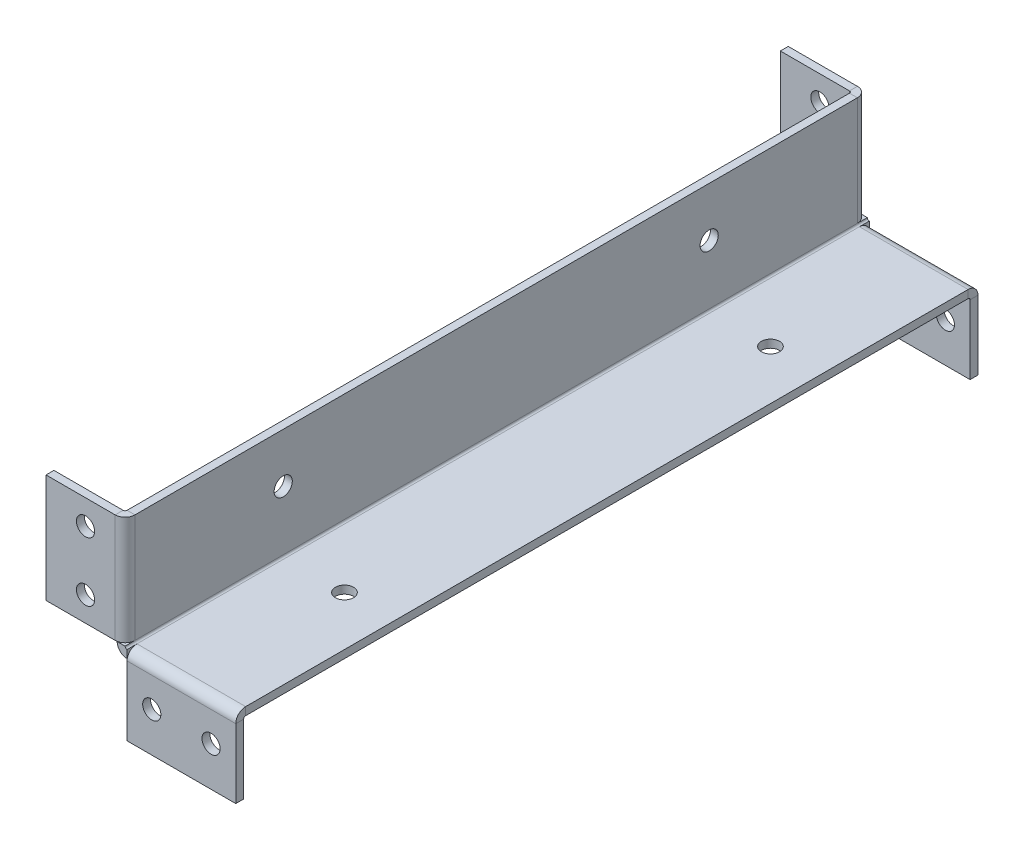
SolidWorks part; units mm, degrees
note: The reader was unsure of these and kept them because the rebuilt part matched: flange length of "Edge-Flange1", "Edge-Flange2".
ref_plane "Front Plane" through (0, 0, 0) normal (0, 0, 1) x (1, 0, 0)
ref_plane "Top Plane" through (0, 0, 0) normal (0, 1, 0) x (1, 0, 0)
ref_plane "Right Plane" through (0, 0, 0) normal (1, 0, 0) x (0, 0, -1)
sketch "Sketch1" plane through (0, 0, 0) normal (0, 1, 0) x (1, 0, 0)
  line L1 (30, 187.75) -> (-30, 187.75)
  line L2 (30, 187.75) -> (30, -187.75)
  line L3 (30, -187.75) -> (-30, -187.75)
  line L4 (-30, 187.75) -> (-30, -187.75)
  line L5 (30, 187.75) -> (-30, -187.75) construction
  line L6 (30, -187.75) -> (-30, 187.75) construction
  point P0 (0, 0)
  dimension "D1" = 60
  dimension "D2" = 375.5
sheet metal parameters "Sheet-Metal1" thickness 4 parameters "D1"=1
base flange "Base-Flange1" sketch "Sketch1" thickness 4 reverse thickness direction yes parameters "D1"=1
edge flange "Edge-Flange1" sketch "Sketch5" flange angle 90 flange length 60 flange position material inside bend radius 1 thickness 4 parameters "D6"=10
sketch "Sketch5" plane through (-30, 4, 0) normal (-1, 0, 0) x (0, 0, 1)
  line L2 (-187.75, 0) -> (-187.75, 56)
  line L3 (-187.75, 56) -> (187.75, 56)
  line L4 (187.75, 56) -> (187.75, 0)
  line L5 (-187.75, 0) -> (187.75, 0) construction
  line L6 (-187.75, 0) -> (187.75, 0)
bend "EdgeBend1" bend radius 1 bend angle 90 parameters "D5"=1
edge flange "Edge-Flange2" sketch "Sketch14" flange profiles "Sketch14", "Sketch15", "Sketch16", "Sketch17" flange angle 90 flange length 40 flange position material inside bend radius 1 thickness 4 relief none parameters "D6"=10, "D8"=0.5
sketch "Sketch14" plane through (-30, 0, 187.75) normal (0, 0, -1) x (0, -1, 0)
  line L1 (-5, 0) -> (-60, 0) construction
  line L2 (-60, 0) -> (-60, 36)
  line L3 (-60, 36) -> (-5, 36)
  line L4 (-5, 36) -> (-5, 0)
  line L5 (-5, 0) -> (-60, 0)
sketch "Sketch15" plane through (0, 0, 187.75) normal (0, 0, -1) x (1, 0, 0)
  line L0 (30, 0) -> (-25, 0) construction
  line L1 (30, 0) -> (-25, 0)
  line L2 (30, 0) -> (30, 36)
  line L3 (30, 36) -> (-25, 36)
  line L4 (-25, 36) -> (-25, 0)
sketch "Sketch16" plane through (-30, 0, -187.75) normal (0, 0, 1) x (0, 1, 0)
  line L0 (60, 0) -> (5, 0) construction
  line L1 (60, 0) -> (5, 0)
  line L2 (60, 0) -> (60, 36)
  line L3 (60, 36) -> (5, 36)
  line L4 (5, 36) -> (5, 0)
sketch "Sketch17" plane through (0, 0, -187.75) normal (0, 0, 1) x (-1, 0, 0)
  line L0 (25, 0) -> (-30, 0) construction
  line L1 (25, 0) -> (-30, 0)
  line L2 (25, 0) -> (25, 36)
  line L3 (25, 36) -> (-30, 36)
  line L4 (-30, 36) -> (-30, 0)
bend "EdgeBend2" bend radius 1 bend angle 90 parameters "D5"=2
bend "EdgeBend3" bend radius 1 bend angle 90 parameters "D5"=3
bend "EdgeBend4" bend radius 1 bend angle 90 parameters "D5"=4
bend "EdgeBend5" bend radius 1 bend angle 90 parameters "D5"=5
sketch "Sketch18" plane through (0, 0, 187.75) normal (0, 0, 1) x (1, 0, 0)
  line L0 (-25, 4) -> (30, 4) construction
  line L1 (-26, 60) -> (-26, 5) construction
  line L2 (-66, 60) -> (-31, 60) construction
  line L3 (30, -1) -> (30, -36) construction
  circle A0 centre (-46, 47.5) radius 4.6
  circle A1 centre (-46, 17.5) radius 4.6
  circle A2 centre (-12.5, -16) radius 4.6
  circle A3 centre (17.5, -16) radius 4.6
  dimension "D7" = 9.2
  dimension "D1" = 30
  dimension "D2" = 30
  dimension "D3" = 20
  dimension "D4" = 20
  dimension "D5" = 12.5
  dimension "D6" = 12.5
extrude "Extrude1" cut sketch "Sketch18" against normal through all normal cut yes
sketch "Sketch19" plane through (-26, 0, 0) normal (1, 0, 0) x (0, 0, -1)
  line L0 (-182.75, 60) -> (182.75, 60) construction
  line L1 (-187.75, 5) -> (-187.75, 60) construction
  line L2 (187.75, 5) -> (187.75, 60) construction
  circle A0 centre (-107.75, 35) radius 4.6
  circle A1 centre (107.75, 35) radius 4.6
  dimension "D4" = 9.2
  dimension "D1" = 25
  dimension "D2" = 80
  dimension "D3" = 80
extrude "Extrude2" cut sketch "Sketch19" against normal blind 4 normal cut yes
sketch "Sketch20" plane through (0, 4, 0) normal (0, 1, 0) x (1, 0, 0)
  line L0 (30, -182.75) -> (30, 182.75) construction
  line L1 (-25, -187.75) -> (30, -187.75) construction
  line L2 (30, 187.75) -> (-25, 187.75) construction
  circle A0 centre (5, 107.75) radius 4.6
  circle A1 centre (5, -107.75) radius 4.6
  dimension "D2" = 9.2
  dimension "D1" = 25
  dimension "D3" = 80
  dimension "D4" = 80
extrude "Extrude3" cut sketch "Sketch20" against normal blind 4 normal cut yes
flat pattern "Flat-Pattern1" [suppressed]
sketch "Bend-Lines1" plane through (0, 4, 0) normal (0, 1, 0) x (-1, 0, 0)
  line L0 (25, -199.4012) -> (-30, -199.4012) construction
  line L1 (82.8023, -199.4012) -> (27.8023, -199.4012) construction
  line L2 (-30, 199.4012) -> (25, 199.4012) construction
  line L3 (27.8023, 199.4012) -> (82.8023, 199.4012) construction
  line L4 (26.4012, -203) -> (26.4012, 203) construction
  line L5 (25, -199.4012) -> (-30, -199.4012) construction
  line L6 (82.8023, -199.4012) -> (27.8023, -199.4012) construction
  line L7 (-30, 199.4012) -> (25, 199.4012) construction
  line L8 (27.8023, 199.4012) -> (82.8023, 199.4012) construction
  line L9 (26.4012, -203) -> (26.4012, 203) construction
sketch3d "Bounding-Box1" [suppressed]
  line L0 (52.8023, 32.8023, 0) -> (52.8023, -438.8023, 0) construction
  line L1 (-60, 32.8023, 0) -> (-60, -438.8023, 0) construction
  line L2 (52.8023, 32.8023, 0) -> (-60, 32.8023, 0) construction
  line L3 (52.8023, -438.8023, 0) -> (-60, -438.8023, 0) construction
bend of the flat pattern "Flatten-<EdgeBend1>1"
bend of the flat pattern "Flatten-<EdgeBend2>1"
bend of the flat pattern "Flatten-<EdgeBend3>1"
bend of the flat pattern "Flatten-<EdgeBend4>1"
bend of the flat pattern "Flatten-<EdgeBend5>1"
